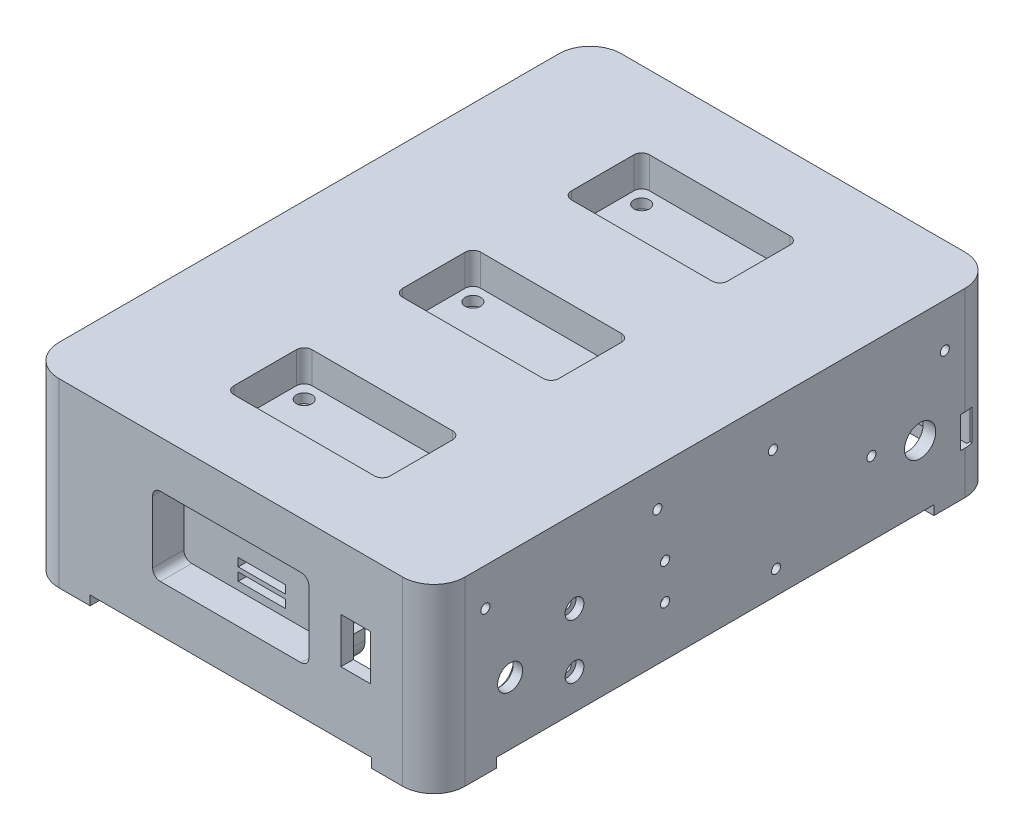
SolidWorks part; units mm, degrees
ref_plane "Спереди" through (0, 0, 0) normal (0, 0, 1) x (1, 0, 0)
ref_plane "Сверху" through (0, 0, 0) normal (0, 1, 0) x (1, 0, 0)
ref_plane "Справа" through (0, 0, 0) normal (1, 0, 0) x (0, 0, -1)
sketch "Эскиз1" plane through (0, 0, 0) normal (0, 1, 0) x (1, 0, 0)
  line L1 (-65, -90) -> (65, -90)
  line L2 (-65, -90) -> (-65, 90)
  line L3 (-65, 90) -> (65, 90)
  line L4 (65, -90) -> (65, 90)
  line L5 (-65, -90) -> (65, 90) construction
  line L6 (-65, 90) -> (65, -90) construction
  point P0 (0, 0)
  dimension "D1" = 130
  dimension "D2" = 180
extrude "Бобышка-Вытянуть1" add sketch "Эскиз1" along normal blind 55
sketch "Эскиз2" plane through (0, 0, 90) normal (0, 0, 1) x (1, 0, 0)
  line L0 (-1050, 27.5) -> (48950, 27.5) construction
  line L1 (-65, 55) -> (-65, 0) construction
  line L2 (0, -999.2777) -> (0, 49000.7223) construction
  line L4 (-22.5, 15) -> (22.5, 15)
  line L5 (-25, 17.5) -> (-25, 37.5)
  line L6 (-22.5, 40) -> (22.5, 40)
  line L7 (25, 17.5) -> (25, 37.5)
  line L8 (-25, 15) -> (25, 40) construction
  line L9 (-25, 40) -> (25, 15) construction
  arc A0 (-22.5, 40) -> (-25, 37.5) centre (-22.5, 37.5) ccw
  arc A1 (-25, 17.5) -> (-22.5, 15) centre (-22.5, 17.5) ccw
  arc A2 (25, 17.5) -> (22.5, 15) centre (22.5, 17.5) cw
  arc A3 (25, 37.5) -> (22.5, 40) centre (22.5, 37.5) ccw
  point P5 (-65, 27.5)
  point P6 (0, 27.5)
  dimension "D3" = 2.5
  dimension "D4" = 2.5
  dimension "D1" = 25
  dimension "D2" = 50
extrude "Вырез-Вытянуть1" cut sketch "Эскиз2" against normal blind 10
sketch "Эскиз4" plane through (0, 55, 0) normal (0, 1, 0) x (1, 0, 0)
  line L0 (0, -1000) -> (0, 49000) construction
  line L1 (-1000, 0) -> (49000, 0) construction
  line L2 (-22.5, 41.5) -> (22.5, 41.5)
  line L3 (-25, 44) -> (-25, 64)
  line L4 (-22.5, 66.5) -> (22.5, 66.5)
  line L5 (-22.5, -12.5) -> (22.5, -12.5)
  line L6 (-25, -10) -> (-25, 10)
  line L7 (-22.5, 12.5) -> (22.5, 12.5)
  line L8 (25, -10) -> (25, 10)
  line L9 (-25, -12.5) -> (25, 12.5) construction
  line L10 (-25, 12.5) -> (25, -12.5) construction
  line L11 (25, 44) -> (25, 64)
  line L12 (-25, 41.5) -> (25, 66.5) construction
  line L13 (-25, 66.5) -> (25, 41.5) construction
  line L14 (-25, -12.5) -> (25, -12.5) [skipped]
  line L15 (-25, -12.5) -> (-25, 12.5) [skipped]
  line L16 (-25, 12.5) -> (25, 12.5) [skipped]
  line L17 (25, -12.5) -> (25, 12.5) [skipped]
  line L18 (-25, -12.5) -> (25, 12.5) construction
  line L19 (-25, 12.5) -> (25, -12.5) construction
  line L20 (-22.5, -66.5) -> (22.5, -66.5)
  line L21 (-25, -64) -> (-25, -44)
  line L22 (-22.5, -41.5) -> (22.5, -41.5)
  line L23 (25, -64) -> (25, -44)
  line L24 (-25, -66.5) -> (25, -41.5) construction
  line L25 (-25, -41.5) -> (25, -66.5) construction
  arc A0 (22.5, -41.5) -> (25, -44) centre (22.5, -44) cw
  arc A1 (25, -64) -> (22.5, -66.5) centre (22.5, -64) cw
  arc A2 (-22.5, -66.5) -> (-25, -64) centre (-22.5, -64) cw
  arc A3 (-25, -44) -> (-22.5, -41.5) centre (-22.5, -44) cw
  arc A4 (-25, 64) -> (-22.5, 66.5) centre (-22.5, 64) cw
  arc A5 (-22.5, 12.5) -> (-25, 10) centre (-22.5, 10) ccw
  arc A6 (25, -10) -> (22.5, -12.5) centre (22.5, -10) cw
  arc A7 (22.5, 66.5) -> (25, 64) centre (22.5, 64) cw
  arc A8 (25, 44) -> (22.5, 41.5) centre (22.5, 44) cw
  arc A9 (-22.5, 41.5) -> (-25, 44) centre (-22.5, 44) cw
  arc A10 (22.5, 12.5) -> (25, 10) centre (22.5, 10) cw
  arc A11 (-22.5, -12.5) -> (-25, -10) centre (-22.5, -10) cw
  point P8 (0, 0)
  point P9 (0, 54)
  point P18 (0, 0)
  point P23 (0, -54)
  dimension "D7" = 2.5
  dimension "D8" = 2.5
  dimension "D1" = 25
  dimension "D2" = 50
  dimension "D5" = 41.5
  dimension "D6" = 41.5
  dimension "D3" = 2
  dimension "D4" = 2
extrude "Вырез-Вытянуть2" cut sketch "Эскиз4" against normal blind 10
mirror "Зеркальное отражение1" about plane through (0, 0, 0) normal (0, 0, 1) of "Вырез-Вытянуть1"
shell "Оболочка1" thickness 4 removed face at (0, 0, 0)
sketch "Эскиз5" plane through (-65, 0, 0) normal (-1, 0, 0) x (0, 0, 1)
  line L0 (45, 28.75) -> (45, 11.25) construction
  line L2 (90, 55) -> (90, 0) construction
  line L4 (-90, 0) -> (90, 0) construction
  line L7 (-1075, 20) -> (48925, 20) construction
  line L8 (-90, 55) -> (-90, 0) construction
  circle A3 centre (45, 28.75) radius 1.45
  circle A4 centre (45, 11.25) radius 1.45
  circle A5 centre (65.6, 20) radius 4
  circle A6 centre (-65.6, 20) radius 5
  dimension "D2" = 17.5
  dimension "D3" = 20
  dimension "D6" = 10
  dimension "D1" = 17.5
  dimension "D5" = 2.9
  dimension "D9" = 45
  dimension "D10" = 20.6
  dimension "D11" = 8
  dimension "D4" = 24.4
extrude "Вырез-Вытянуть3" cut sketch "Эскиз5" against normal blind 15
sketch "Эскиз6" plane through (-65, 0, 0) normal (-1, 0, 0) x (0, 0, 1)
  circle A2 centre (45, 28.75) radius 3
  circle A3 centre (45, 11.25) radius 3
  dimension "D1" = 6
extrude "Вырез-Вытянуть4" cut sketch "Эскиз6" against normal blind 2.5
sketch "Эскиз11" plane through (-61, 0, 0) normal (1, 0, 0) x (0, 0, -1)
  circle A1 centre (-65.6, 20) radius 5
  dimension "D1" = 10
extrude "Вырез-Вытянуть16" cut sketch "Эскиз11" against normal blind 1
mirror "Зеркальное отражение2" about plane through (0, 0, 0) normal (1, 0, 0) of "Вырез-Вытянуть3", "Вырез-Вытянуть4", "Вырез-Вытянуть16"
sketch "Эскиз12" plane through (0, 11, 0) normal (0, -1, 0) x (-1, 0, 0)
  line L0 (-1014.7864, -78) -> (48985.2136, -78) construction
  line L1 (22.5, -76) -> (-22.5, -76) construction
  line L2 (0, -1061) -> (0, 48939) construction
  line L3 (-10, -1061) -> (-10, 48939) construction
  line L4 (10, -1061) -> (10, 48939) construction
  circle A0 centre (-10, -78) radius 1.45
  circle A1 centre (10, -78) radius 1.45
  point P7 (0, -76)
  dimension "D4" = 2.9
  dimension "D1" = 2
  dimension "D2" = 20
  dimension "D3" = 10
extrude "Вырез-Вытянуть17" cut sketch "Эскиз12" against normal blind 14
sketch "Эскиз15" plane through (0, 45, 0) normal (0, 1, 0) x (1, 0, 0)
  line L0 (-1010.1672, -62.5) -> (48989.8328, -62.5) construction
  line L1 (0, -1031.5) -> (0, 48968.5) construction
  line L2 (-7.6, -63.8) -> (7.6, -63.8)
  line L3 (-7.6, -63.8) -> (-7.6, -61.2)
  line L4 (-7.6, -61.2) -> (7.6, -61.2)
  line L5 (7.6, -63.8) -> (7.6, -61.2)
  line L6 (-7.6, -63.8) -> (7.6, -61.2) construction
  line L7 (-7.6, -61.2) -> (7.6, -63.8) construction
  line L8 (22.5, -41.5) -> (-22.5, -41.5) construction
  line L9 (-22.5, -66.5) -> (22.5, -66.5) construction
  line L10 (-7.6, -9.8) -> (7.6, -9.8)
  line L11 (-7.6, -9.8) -> (-7.6, -7.2)
  line L12 (-7.6, -7.2) -> (7.6, -7.2)
  line L13 (7.6, -9.8) -> (7.6, -7.2)
  line L14 (-7.6, -9.8) -> (7.6, -7.2) construction
  line L15 (-7.6, -7.2) -> (7.6, -9.8) construction
  line L16 (-7.6, 44.2) -> (7.6, 44.2)
  line L17 (-7.6, 44.2) -> (-7.6, 46.8)
  line L18 (-7.6, 46.8) -> (7.6, 46.8)
  line L19 (7.6, 44.2) -> (7.6, 46.8)
  line L20 (-7.6, 44.2) -> (7.6, 46.8) construction
  line L21 (-7.6, 46.8) -> (7.6, 44.2) construction
  line L23 (22.5, 12.5) -> (-22.5, 12.5) construction
  line L24 (-7.6, -59.8) -> (7.6, -59.8)
  line L25 (-7.6, -59.8) -> (-7.6, -57.2)
  line L26 (-7.6, -57.2) -> (7.6, -57.2)
  line L27 (7.6, -59.8) -> (7.6, -57.2)
  line L28 (-7.6, -59.8) -> (7.6, -57.2) construction
  line L29 (-7.6, -57.2) -> (7.6, -59.8) construction
  line L30 (-7.6, -5.8) -> (7.6, -5.8)
  line L31 (-7.6, -5.8) -> (-7.6, -3.2)
  line L32 (-7.6, -3.2) -> (7.6, -3.2)
  line L33 (7.6, -5.8) -> (7.6, -3.2)
  line L34 (-7.6, -5.8) -> (7.6, -3.2) construction
  line L35 (-7.6, -3.2) -> (7.6, -5.8) construction
  line L36 (-7.6, 48.2) -> (7.6, 48.2)
  line L37 (-7.6, 48.2) -> (-7.6, 50.8)
  line L38 (-7.6, 50.8) -> (7.6, 50.8)
  line L39 (7.6, 48.2) -> (7.6, 50.8)
  line L40 (-7.6, 48.2) -> (7.6, 50.8) construction
  line L41 (-7.6, 50.8) -> (7.6, 48.2) construction
  line L42 (-22.5, -12.5) -> (22.5, -12.5) construction
  circle A0 centre (-20, -46.5) radius 2.5
  circle A1 centre (20, -46.5) radius 2.5
  circle A2 centre (-20, 7.5) radius 2.5
  circle A3 centre (20, 7.5) radius 2.5
  circle A4 centre (-20, 61.5) radius 2.5
  circle A5 centre (20, 61.5) radius 2.5
  point P1 (0, -62.5)
  point P12 (0, -41.5)
  point P16 (0, -8.5)
  point P21 (0, 45.5)
  point P41 (0, -4.5)
  point P42 (0, -58.5)
  point P51 (0, 49.5)
  dimension "D6" = 40
  dimension "D8" = 5
  dimension "D1" = 2.6
  dimension "D2" = 15.2
  dimension "D3" = 4
  dimension "D4" = 3
  dimension "D5" = 4
  dimension "D7" = 40
  dimension "D9" = 5
  dimension "D10" = 3
  dimension "D11" = 5
  dimension "D13" = 4
  dimension "D15" = 4
  dimension "D12" = 2
  dimension "D14" = 3
extrude "Вырез-Вытянуть20" cut sketch "Эскиз15" against normal blind 3
sketch "Эскиз16" plane through (0, 42, 0) normal (0, 1, 0) x (1, 0, 0)
  line L0 (-7.6, -62.5) -> (7.6, -62.5) construction
  line L1 (-7.6, -61.2) -> (-7.6, -63.8) construction
  line L2 (7.6, -63.8) -> (7.6, -61.2) construction
  line L3 (0, -1000) -> (0, 49000) construction
  line L4 (-7, -63.4) -> (7, -63.4)
  line L5 (-7, -63.4) -> (-7, -61.6)
  line L6 (-7, -61.6) -> (7, -61.6)
  line L7 (7, -63.4) -> (7, -61.6)
  line L8 (-7, -63.4) -> (7, -61.6) construction
  line L9 (-7, -61.6) -> (7, -63.4) construction
  line L10 (-7, -9.4) -> (7, -9.4)
  line L11 (-7, -9.4) -> (-7, -7.6)
  line L12 (-7, -7.6) -> (7, -7.6)
  line L13 (7, -9.4) -> (7, -7.6)
  line L14 (-7.6, -8.5) -> (7.6, -8.5) construction
  line L15 (-7, -9.4) -> (7, -7.6) construction
  line L16 (-7, -7.6) -> (7, -9.4) construction
  line L17 (-7, 44.6) -> (7, 44.6)
  line L18 (-7, 44.6) -> (-7, 46.4)
  line L19 (-7, 46.4) -> (7, 46.4)
  line L20 (7, 44.6) -> (7, 46.4)
  line L21 (-7.6, 45.5) -> (7.6, 45.5) construction
  line L22 (-7, 44.6) -> (7, 46.4) construction
  line L23 (-7, 46.4) -> (7, 44.6) construction
  line L24 (-7.6, -7.2) -> (-7.6, -9.8) construction
  line L25 (-7.6, -58.5) -> (7.6, -58.5) construction
  line L26 (-7, -59.4) -> (7, -59.4)
  line L27 (-7, -59.4) -> (-7, -57.6)
  line L28 (-7, -57.6) -> (7, -57.6)
  line L29 (7, -59.4) -> (7, -57.6)
  line L30 (-7, -59.4) -> (7, -57.6) construction
  line L31 (-7, -57.6) -> (7, -59.4) construction
  line L32 (-7.6, -57.2) -> (-7.6, -59.8) construction
  line L33 (7.6, -59.8) -> (7.6, -57.2) construction
  line L34 (-7.6, -4.5) -> (7.6, -4.5) construction
  line L35 (-7.6, -3.2) -> (-7.6, -5.8) construction
  line L36 (7.6, -5.8) -> (7.6, -3.2) construction
  line L37 (-7.6, -9.8) -> (7.6, -9.8) construction
  line L38 (-7, -5.4) -> (7, -5.4)
  line L39 (-7, -5.4) -> (-7, -3.6)
  line L40 (-7, -3.6) -> (7, -3.6)
  line L41 (7, -5.4) -> (7, -3.6)
  line L42 (-7, -5.4) -> (7, -3.6) construction
  line L43 (-7, -3.6) -> (7, -5.4) construction
  line L44 (7.6, -9.8) -> (7.6, -7.2) construction
  line L45 (-7.6, 46.8) -> (-7.6, 44.2) construction
  line L46 (7.6, 44.2) -> (7.6, 46.8) construction
  line L47 (-7.6, 44.2) -> (7.6, 44.2) construction
  line L48 (-7.6, 49.5) -> (7.6, 49.5) construction
  line L49 (-7.6, 50.8) -> (-7.6, 48.2) construction
  line L50 (7.6, 48.2) -> (7.6, 50.8) construction
  line L52 (-7, 48.6) -> (7, 48.6)
  line L53 (-7, 48.6) -> (-7, 50.4)
  line L54 (-7, 50.4) -> (7, 50.4)
  line L55 (7, 48.6) -> (7, 50.4)
  line L56 (-7, 48.6) -> (7, 50.4) construction
  line L57 (-7, 50.4) -> (7, 48.6) construction
  point P6 (0, -62.5)
  point P12 (0, -58.5)
  point P17 (0, -8.5)
  point P24 (0, 36.6)
  point P41 (0, -4.5)
  point P54 (0, 49.5)
  dimension "D1" = 1.8
  dimension "D2" = 14
  dimension "D4" = 0.4
  dimension "D3" = 0.4
extrude "Вырез-Вытянуть21" cut sketch "Эскиз16" against normal blind 3
sketch "Эскиз17" plane through (0, 0, 80) normal (0, 0, 1) x (1, 0, 0)
  line L0 (-7.6, 17.5) -> (7.6, 17.5)
  line L1 (-7.6, 17.5) -> (-7.6, 20.1)
  line L2 (-7.6, 20.1) -> (7.6, 20.1)
  line L3 (7.6, 17.5) -> (7.6, 20.1)
  line L4 (-7.6, 17.5) -> (7.6, 20.1) construction
  line L5 (-7.6, 20.1) -> (7.6, 17.5) construction
  line L7 (-7.6, 21.5) -> (7.6, 21.5)
  line L8 (-22.5, 15) -> (22.5, 15) construction
  line L9 (0, -965) -> (0, 49035) construction
  line L10 (22.5, 40) -> (-22.5, 40) construction
  line L11 (-7.6, 21.5) -> (-7.6, 24.1)
  line L12 (-7.6, 24.1) -> (7.6, 24.1)
  line L13 (7.6, 21.5) -> (7.6, 24.1)
  line L14 (-7.6, 21.5) -> (7.6, 24.1) construction
  line L15 (-7.6, 24.1) -> (7.6, 21.5) construction
  circle A0 centre (-20, 35) radius 2.5
  circle A1 centre (20, 35) radius 2.5
  point P0 (0, 18.8)
  point P11 (0, 22.8)
  point P20 (0, 40)
  dimension "D5" = 5
  dimension "D8" = 4
  dimension "D1" = 2.6
  dimension "D2" = 15.2
  dimension "D3" = 40
  dimension "D4" = 40
  dimension "D6" = 2.5
  dimension "D7" = 5
extrude "Вырез-Вытянуть22" cut sketch "Эскиз17" against normal blind 3
sketch "Эскиз18" plane through (0, 0, 77) normal (0, 0, 1) x (1, 0, 0)
  line L0 (-7.6, 18.8) -> (7.6, 18.8) construction
  line L1 (-7.6, 20.1) -> (-7.6, 17.5) construction
  line L2 (7.6, 17.5) -> (7.6, 20.1) construction
  line L3 (0, -980.9) -> (0, 49019.1) construction
  line L4 (-7, 17.9) -> (7, 17.9)
  line L5 (-7, 17.9) -> (-7, 19.7)
  line L6 (-7, 19.7) -> (7, 19.7)
  line L7 (7, 17.9) -> (7, 19.7)
  line L8 (-7, 17.9) -> (7, 19.7) construction
  line L9 (-7, 19.7) -> (7, 17.9) construction
  line L10 (7.6, 24.1) -> (-7.6, 24.1) construction
  line L12 (-7, 21.9) -> (7, 21.9)
  line L13 (-7, 21.9) -> (-7, 23.7)
  line L14 (-7, 23.7) -> (7, 23.7)
  line L15 (7, 21.9) -> (7, 23.7)
  line L16 (-7, 21.9) -> (7, 23.7) construction
  line L17 (-7, 23.7) -> (7, 21.9) construction
  point P6 (0, 18.8)
  point P12 (0, 22.8)
  point P16 (0, 24.1)
  dimension "D1" = 1.8
  dimension "D2" = 14
  dimension "D3" = 4
extrude "Вырез-Вытянуть23" cut sketch "Эскиз18" against normal blind 3
sketch "Эскиз19" plane through (0, 0, -80) normal (0, 0, -1) x (1, 0, 0)
  line L0 (-7.6, -37.5) -> (7.6, -37.5)
  line L1 (-7.6, -37.5) -> (-7.6, -34.9)
  line L2 (-7.6, -34.9) -> (7.6, -34.9)
  line L3 (7.6, -37.5) -> (7.6, -34.9)
  line L4 (-7.6, -37.5) -> (7.6, -34.9) construction
  line L5 (-7.6, -34.9) -> (7.6, -37.5) construction
  line L6 (0, -1010) -> (0, 48990) construction
  line L7 (-22.5, -15) -> (22.5, -15) construction
  line L9 (-7.6, -33.5) -> (7.6, -33.5)
  line L10 (22.5, -40) -> (-22.5, -40) construction
  line L11 (-7.6, -33.5) -> (-7.6, -30.9)
  line L12 (-7.6, -30.9) -> (7.6, -30.9)
  line L13 (7.6, -33.5) -> (7.6, -30.9)
  line L14 (-7.6, -33.5) -> (7.6, -30.9) construction
  line L15 (-7.6, -30.9) -> (7.6, -33.5) construction
  circle A0 centre (-20, -20) radius 2.5
  circle A1 centre (20, -20) radius 2.5
  point P0 (0, -36.2)
  point P14 (0, -15)
  point P16 (0, -32.2)
  dimension "D5" = 5
  dimension "D7" = 2.5
  dimension "D1" = 2.6
  dimension "D2" = 15.2
  dimension "D3" = 40
  dimension "D4" = 40
  dimension "D6" = 5
  dimension "D8" = 4
extrude "Вырез-Вытянуть24" cut sketch "Эскиз19" against normal blind 3
sketch "Эскиз20" plane through (0, 0, -77) normal (0, 0, -1) x (1, 0, 0)
  line L0 (-1007.6, -36.2) -> (48992.4, -36.2) construction
  line L1 (-7.6, -34.9) -> (-7.6, -37.5) construction
  line L3 (-7, -37.1) -> (7, -37.1)
  line L4 (-7, -37.1) -> (-7, -35.3)
  line L5 (-7, -35.3) -> (7, -35.3)
  line L6 (7, -37.1) -> (7, -35.3)
  line L7 (-7, -37.1) -> (7, -35.3) construction
  line L8 (-7, -35.3) -> (7, -37.1) construction
  line L9 (-7, -31.3) -> (7, -31.3)
  line L10 (0, -1029.9) -> (0, 48970.1) construction
  line L11 (7.6, -34.9) -> (-7.6, -34.9) construction
  line L12 (-7, -31.3) -> (-7, -33.1)
  line L13 (-7, -33.1) -> (7, -33.1)
  line L14 (7, -31.3) -> (7, -33.1)
  line L15 (-7, -31.3) -> (7, -33.1) construction
  line L16 (-7, -33.1) -> (7, -31.3) construction
  point P1 (0, -36.2)
  point P5 (-7.6, -36.2)
  point P10 (0, -32.2)
  point P18 (0, -34.9)
  dimension "D1" = 1.8
  dimension "D2" = 14
  dimension "D3" = 4
extrude "Вырез-Вытянуть25" cut sketch "Эскиз20" against normal blind 5
sketch "Эскиз21" plane through (0, 0, 90) normal (0, 0, -1) x (1, 0, 0)
  line L0 (-975, -27.5) -> (49025, -27.5) construction
  line L1 (35.25, -34.75) -> (44.75, -34.75)
  line L2 (35.25, -34.75) -> (35.25, -20.25)
  line L3 (35.25, -20.25) -> (44.75, -20.25)
  line L4 (44.75, -34.75) -> (44.75, -20.25)
  line L5 (35.25, -34.75) -> (44.75, -20.25) construction
  line L6 (35.25, -20.25) -> (44.75, -34.75) construction
  line L7 (25, -17.5) -> (25, -37.5) construction
  line L8 (40, -1022.5) -> (40, 48977.5) construction
  line L9 (65, -55) -> (65, 0) construction
  point P0 (40, -27.5)
  point P10 (25, -27.5)
  dimension "D1" = 9.5
  dimension "D2" = 14.5
  dimension "D3" = 25
extrude "Вырез-Вытянуть26" cut sketch "Эскиз21" along normal blind 4
sketch "Эскиз22" plane through (0, 0, 0) normal (0, -1, 0) x (-1, 0, 0)
  line L0 (-63, -925) -> (-63, 49075) construction
  line L2 (-65, -90) -> (-65, 90) construction
  line L3 (-1046.2998, 88) -> (48953.7002, 88) construction
  line L4 (-65, 90) -> (65, 90) construction
  line L5 (63, -925) -> (63, 49075) construction
  line L6 (65, 90) -> (65, -90) construction
  line L7 (-1052.5, -88) -> (48947.5, -88) construction
  line L8 (65, -90) -> (-65, -90) construction
  line L9 (0, -925) -> (0, 49075) construction
  line L10 (-1052.5, 0) -> (48947.5, 0) construction
  circle A4 centre (0, 88) radius 1.425
  circle A5 centre (0, -88) radius 1.425
  circle A6 centre (-63, 0) radius 1.425
  circle A7 centre (63, 0) radius 1.425
  point P27 (0, 90)
  point P34 (-65, 0)
  dimension "D5" = 2.85
  dimension "D1" = 2
  dimension "D2" = 2
  dimension "D3" = 2
  dimension "D4" = 2
extrude "Вырез-Вытянуть27" cut sketch "Эскиз22" against normal blind 9
sketch "Эскиз24" plane through (-65, 0, 0) normal (-1, 0, 0) x (0, 0, 1)
  line L0 (0, -1000) -> (0, 49000) construction
  line L1 (16, -988.2808) -> (16, 49011.7192) construction
  line L2 (-90, 0) -> (90, 0) construction
  circle A0 centre (16, 16) radius 1.475
  circle A1 centre (16, 27.5) radius 1.475
  dimension "D4" = 2.95
  dimension "D1" = 11.5
  dimension "D2" = 16
  dimension "D3" = 16
extrude "Вырез-Вытянуть28" cut sketch "Эскиз24" against normal through all
fillet "Скругление1" radius 10 4 edges at (65, 27.5, -90) (-65, 27.5, -90) (65, 27.5, 90) (-65, 27.5, 90)
sketch "Эскиз26" plane through (61, 0, 0) normal (-1, 0, 0) x (0, 0, 1)
  line L1 (17.6454, 18.85) -> (14.3546, 18.85)
  line L2 (14.3546, 18.85) -> (12.7091, 16)
  line L3 (12.7091, 16) -> (14.3546, 13.15)
  line L4 (14.3546, 13.15) -> (17.6454, 13.15)
  line L5 (17.6454, 13.15) -> (19.2909, 16)
  line L6 (19.2909, 16) -> (17.6454, 18.85)
  line L7 (17.6454, 30.35) -> (14.3546, 30.35)
  line L8 (14.3546, 30.35) -> (12.7091, 27.5)
  line L9 (12.7091, 27.5) -> (14.3546, 24.65)
  line L10 (14.3546, 24.65) -> (17.6454, 24.65)
  line L11 (17.6454, 24.65) -> (19.2909, 27.5)
  line L12 (19.2909, 27.5) -> (17.6454, 30.35)
  circle A0 centre (16, 16) radius 2.85 construction
  circle A1 centre (16, 27.5) radius 2.85 construction
  dimension "D1" = 5.7
extrude "Вырез-Вытянуть29" cut sketch "Эскиз26" against normal blind 2 and the other way blind 124
fillet "Скругление2" radius 3 4 edges at (61, 25.5, 86) (61, 25.5, -86) (-61, 25.5, -86) (-61, 25.5, 86)
sketch "Эскиз27" plane through (0, 0, 0) normal (0, -1, 0) x (1, 0, 0)
  line L0 (-55, -90) -> (-45, -90)
  line L1 (55, -90) -> (-55, -90) construction
  line L2 (-45, -90) -> (-45, -86)
  line L3 (58, -86) -> (-58, -86) construction
  line L4 (-45, -86) -> (-58, -86)
  line L6 (-61, -83) -> (-61, -70)
  line L7 (-61, -83) -> (-61, 83) construction
  line L8 (-61, -70) -> (-65, -70)
  line L9 (-65, -80) -> (-65, 80) construction
  line L10 (-65, -70) -> (-65, -80)
  line L11 (0, -1000) -> (0, 49000) construction
  line L12 (-1000, 0) -> (49000, 0) construction
  line L13 (65, -70) -> (65, -80)
  line L14 (61, -70) -> (65, -70)
  line L15 (61, -83) -> (61, -70)
  line L16 (45, -86) -> (58, -86)
  line L17 (45, -90) -> (45, -86)
  line L18 (55, -90) -> (45, -90)
  line L19 (55, 90) -> (45, 90)
  line L20 (45, 90) -> (45, 86)
  line L21 (45, 86) -> (58, 86)
  line L22 (61, 83) -> (61, 70)
  line L23 (61, 70) -> (65, 70)
  line L24 (65, 70) -> (65, 80)
  line L25 (-65, 70) -> (-65, 80)
  line L26 (-61, 70) -> (-65, 70)
  line L27 (-61, 83) -> (-61, 70)
  line L28 (-45, 86) -> (-58, 86)
  line L29 (-45, 90) -> (-45, 86)
  line L30 (-55, 90) -> (-45, 90)
  arc A1 (-65, -80) -> (-55, -90) centre (-55, -80) ccw construction
  arc A4 (61, -83) -> (58, -86) centre (58, -83) cw
  arc A5 (-65, -80) -> (-55, -90) centre (-55, -80) ccw
  arc A6 (65, -80) -> (55, -90) centre (55, -80) cw
  arc A7 (-61, 83) -> (-58, 86) centre (-58, 83) cw
  arc A8 (-61, -83) -> (-58, -86) centre (-58, -83) ccw construction
  arc A9 (-61, -83) -> (-58, -86) centre (-58, -83) ccw
  arc A10 (65, 80) -> (55, 90) centre (55, 80) ccw
  arc A11 (-65, 80) -> (-55, 90) centre (-55, 80) cw
  arc A12 (61, 83) -> (58, 86) centre (58, 83) ccw
  dimension "D1" = 10
extrude "Бобышка-Вытянуть2" add sketch "Эскиз27" along normal blind 3
sketch "Эскиз28" plane through (0, 0, 0) normal (0, -1, 0) x (1, 0, 0)
  line L0 (-61, 70) -> (-61, 83) construction
  line L2 (-61, 70) -> (-61, 83)
  line L3 (-58, 86) -> (-45, 86)
  line L4 (-45, 86) -> (-45, 86.5)
  line L5 (-45, 86) -> (-45, 90) construction
  line L6 (-45, 86.5) -> (-58, 86.5)
  line L7 (-1000, 0) -> (49000, 0) construction
  line L8 (-61.5, 83) -> (-61.5, 70)
  line L9 (-65, 70) -> (-61, 70) construction
  line L10 (-61.5, 70) -> (-61, 70)
  line L11 (0, -1000) -> (0, 49000) construction
  line L12 (61.5, 70) -> (61, 70)
  line L13 (61.5, 83) -> (61.5, 70)
  line L14 (45, 86.5) -> (58, 86.5)
  line L15 (45, 86) -> (45, 86.5)
  line L16 (58, 86) -> (45, 86)
  line L17 (61, 70) -> (61, 83)
  line L18 (61, -70) -> (61, -83)
  line L19 (58, -86) -> (45, -86)
  line L20 (45, -86) -> (45, -86.5)
  line L21 (45, -86.5) -> (58, -86.5)
  line L22 (61.5, -83) -> (61.5, -70)
  line L23 (61.5, -70) -> (61, -70)
  line L24 (-61.5, -70) -> (-61, -70)
  line L25 (-61.5, -83) -> (-61.5, -70)
  line L26 (-45, -86.5) -> (-58, -86.5)
  line L27 (-45, -86) -> (-45, -86.5)
  line L28 (-58, -86) -> (-45, -86)
  line L29 (-61, -70) -> (-61, -83)
  arc A0 (-58, 86) -> (-61, 83) centre (-58, 83) ccw construction
  arc A1 (-58, 86) -> (-61, 83) centre (-58, 83) ccw
  arc A2 (-61.5, 83) -> (-58, 86.5) centre (-58, 83) cw
  arc A3 (61.5, 83) -> (58, 86.5) centre (58, 83) ccw
  arc A4 (58, 86) -> (61, 83) centre (58, 83) cw
  arc A5 (58, -86) -> (61, -83) centre (58, -83) ccw
  arc A6 (61.5, -83) -> (58, -86.5) centre (58, -83) cw
  arc A7 (-61.5, -83) -> (-58, -86.5) centre (-58, -83) ccw
  arc A8 (-58, -86) -> (-61, -83) centre (-58, -83) cw
  dimension "D1" = 0.5
extrude "Вырез-Вытянуть30" cut sketch "Эскиз28" along normal blind 2.5
sketch "Эскиз30" plane through (0, 51, 0) normal (0, -1, 0) x (1, 0, 0)
  line L0 (-29, -10) -> (-29, 10) construction
  line L1 (-58.5, 86) -> (-29, 86)
  line L2 (-61, 83.5) -> (-61, 6)
  line L3 (-61, 6) -> (-29, 6)
  line L4 (-29, 86) -> (-29, 6)
  line L5 (-58, 86) -> (58, 86) construction
  line L6 (-61, -83) -> (-61, 83) construction
  line L7 (0, -1000) -> (0, 49000) construction
  line L8 (29, 86) -> (29, 6)
  line L9 (61, 6) -> (29, 6)
  line L10 (61, 83.5) -> (61, 6)
  line L11 (58.5, 86) -> (29, 86)
  arc A0 (-58.5, 86) -> (-61, 83.5) centre (-58.5, 83.5) ccw
  arc A1 (58.5, 86) -> (61, 83.5) centre (58.5, 83.5) cw
  dimension "D1" = 2.5
  dimension "D2" = 80
extrude "Вырез-Вытянуть32" cut sketch "Эскиз30" against normal blind 2
sketch "Эскиз29" plane through (-61, 0, 0) normal (1, 0, 0) x (0, 0, -1)
  line L1 (83, 51) -> (-6, 51) construction
  line L2 (-86, 0) -> (-86, 51) construction
  line L3 (0, -1000) -> (0, 49000) construction
  line L4 (90, 55) -> (90, -3) construction
  line L6 (-80, 55) -> (80, 55) construction
  circle A0 centre (-73.5, 43) radius 1.45
  circle A1 centre (-18.5, 43) radius 1.45
  circle A4 centre (18.5, 41) radius 1.45
  circle A5 centre (73.5, 41) radius 1.45
  dimension "D1" = 8
  dimension "D4" = 2.9
  dimension "D5" = 55
  dimension "D2" = 12.5
  dimension "D3" = 55
  dimension "D6" = 16.5
  dimension "D7" = 14
extrude "Вырез-Вытянуть31" cut sketch "Эскиз29" against normal through all both and the other way through all
sketch "Эскиз31" plane through (0, 41, 0) normal (0, -1, 0) x (1, 0, 0)
  line L0 (26, -1043.9084) -> (26, 48956.0916) construction
  line L2 (29, 64) -> (29, 44) construction
  line L3 (29, -76) -> (29, -86) construction
  line L4 (26, 81) -> (29, 81)
  line L5 (26, 81) -> (26, -81)
  line L6 (26, -81) -> (29, -81)
  line L7 (29, 81) -> (29, -81)
  line L8 (22.5, 76) -> (22.5, 86) construction
  line L9 (-977.5, 81) -> (49022.5, 81) construction
  line L10 (0, -1000) -> (0, 49000) construction
  line L11 (-26, -1043.9084) -> (-26, 48956.0916) construction
  line L12 (-29, 81) -> (-29, -81)
  line L13 (-26, -81) -> (-29, -81)
  line L14 (-26, 81) -> (-26, -81)
  line L15 (-26, 81) -> (-29, 81)
  point P16 (22.5, 81)
  dimension "D1" = 3
extrude "Вырез-Вытянуть33" cut sketch "Эскиз31" against normal up to surface (10 mm away) and the other way blind 20 up to face at (0, 51, 27)
sketch "Эскиз32" plane through (61, 0, 0) normal (-1, 0, 0) x (0, 0, 1)
  line L0 (-83, 51) -> (-83, 0) construction
  line L1 (-83, 7) -> (-81.5, 7)
  line L2 (-83, 7) -> (-83, 24.5)
  line L3 (-83, 24.5) -> (-81.5, 24.5)
  line L4 (-81.5, 7) -> (-81.5, 24.5)
  line L5 (83, 0) -> (-83, 0) construction
  dimension "D1" = 17.5
  dimension "D2" = 1.5
  dimension "D3" = 7
extrude "Вырез-Вытянуть34" cut sketch "Эскиз32" against normal blind 3 contours L1 L4 L3 L2
sketch "Эскиз33" plane through (61, 0, 0) normal (-1, 0, 0) x (0, 0, 1)
  line L0 (-81.5, 7) -> (-81.5, 24.5) construction
  line L1 (-82.5, 20.75) -> (-78.5, 20.75)
  line L2 (-82.5, 20.75) -> (-82.5, 10.75)
  line L3 (-82.5, 10.75) -> (-78.5, 10.75)
  line L4 (-78.5, 20.75) -> (-78.5, 10.75)
  line L5 (-1081.5, 15.75) -> (48918.5, 15.75) construction
  point P7 (-78.5, 15.75)
  point P9 (-81.5, 15.75)
  dimension "D1" = 10
  dimension "D2" = 4
  dimension "D3" = 3
extrude "Вырез-Вытянуть35" cut sketch "Эскиз33" against normal blind 4
sketch "Эскиз34" plane through (0, 0, -86) normal (0, 0, 1) x (1, 0, 0)
  line L0 (61, 51) -> (61, 24.5) construction
  line L1 (34, 7) -> (61, 7)
  line L2 (34, 7) -> (34, 24.5)
  line L3 (34, 24.5) -> (61, 24.5)
  line L4 (61, 7) -> (61, 24.5)
  line L5 (58, 0) -> (-58, 0) construction
  dimension "D1" = 7
  dimension "D2" = 27
  dimension "D3" = 17.5
extrude "Бобышка-Вытянуть3" add sketch "Эскиз34" along normal blind 3
sketch "Эскиз35" plane through (61, 0, 0) normal (-1, 0, 0) x (0, 0, 1)
  line L0 (-90, 55) -> (-90, -3) construction
  line L1 (83, 0) -> (-83, 0) construction
  circle A0 centre (-50, 23.5) radius 1.45
  circle A1 centre (-19.5, 7.5) radius 1.45
  dimension "D1" = 16
  dimension "D5" = 2.9
  dimension "D2" = 30.5
  dimension "D3" = 40
  dimension "D4" = 7.5
extrude "Вырез-Вытянуть36" cut sketch "Эскиз35" against normal blind 4
sketch "Эскиз36" plane through (0, 41, 0) normal (0, -1, 0) x (1, 0, 0)
  line L0 (-22.5, 16.5) -> (22.5, 16.5) construction
  line L1 (-17.5, 16.5) -> (17.5, 16.5)
  line L2 (-17.5, 16.5) -> (-17.5, 21.5)
  line L3 (-17.5, 21.5) -> (17.5, 21.5)
  line L4 (17.5, 16.5) -> (17.5, 21.5)
  line L5 (0, -990.6) -> (0, 49009.4) construction
  line L6 (-7, 9.4) -> (7, 9.4) construction
  point P7 (0, 21.5)
  point P11 (0, 9.4)
  dimension "D1" = 5
  dimension "D2" = 35
extrude "Бобышка-Вытянуть4" add sketch "Эскиз36" against normal up to surface (10 mm away)
sketch "Эскиз37" plane through (0, 41, 0) normal (0, -1, 0) x (1, 0, 0)
  line L0 (-14.5, -981.9998) -> (-14.5, 49018.0002) construction
  line L1 (14.5, -981.9998) -> (14.5, 49018.0002) construction
  line L2 (17.5, 21.5) -> (-17.5, 21.5) construction
  circle A0 centre (-14.5, 19.5) radius 1.45
  circle A1 centre (14.5, 19.5) radius 1.45
  dimension "D3" = 2.9
  dimension "D1" = 29
  dimension "D2" = 14.5
  dimension "D4" = 2
extrude "Вырез-Вытянуть37" cut sketch "Эскиз37" against normal blind 6
sketch "Эскиз38" plane through (-61, 0, 0) normal (1, 0, 0) x (0, 0, -1)
  line L0 (-3.9, -995.0619) -> (-3.9, 49004.9381) construction
  line L1 (52, -995.0619) -> (52, 49004.9381) construction
  line L2 (-1004.5398, 26.8) -> (48995.4602, 26.8) construction
  line L3 (-1004.5398, 8) -> (48995.4602, 8) construction
  line L4 (83, 0) -> (-83, 0) construction
  line L5 (86, 51) -> (86, 0) construction
  circle A0 centre (-3.9, 26.8) radius 1.45
  circle A1 centre (-3.9, 8) radius 1.45
  circle A2 centre (52, 8) radius 1.45
  circle A3 centre (52, 26.8) radius 1.45
  point P21 (51.5778, -22.6418)
  point P22 (-1.764, 5.3736)
  dimension "D3" = 2.9
  dimension "D1" = 55.9
  dimension "D2" = 18.8
  dimension "D4" = 8
  dimension "D5" = 34
extrude "Вырез-Вытянуть38" cut sketch "Эскиз38" against normal blind 10
sketch "Эскиз39" plane through (0, 41, 0) normal (0, -1, 0) x (1, 0, 0)
  line L1 (-26, -4) -> (-21, -4)
  line L2 (-26, -4) -> (-26, -11.5)
  line L3 (-26, -11.5) -> (-21, -11.5)
  line L4 (-21, -4) -> (-21, -11.5)
  line L5 (-26, -15.4772) -> (-26, 15.4772) construction
  line L6 (22.5, -16.5) -> (-22.5, -16.5) construction
  line L7 (-26, -38.5228) -> (-26, -69.4772) construction
  line L8 (-26, -61) -> (-21, -61)
  line L9 (-26, -61) -> (-26, -68.5)
  line L10 (-26, -68.5) -> (-21, -68.5)
  line L11 (-21, -61) -> (-21, -68.5)
  line L12 (22.5, -70.5) -> (-22.5, -70.5) construction
  line L13 (0, -1000) -> (0, 49000) construction
  line L14 (21, -61) -> (21, -68.5)
  line L15 (26, -68.5) -> (21, -68.5)
  line L16 (26, -61) -> (26, -68.5)
  line L17 (26, -61) -> (21, -61)
  line L18 (21, -4) -> (21, -11.5)
  line L19 (26, -11.5) -> (21, -11.5)
  line L20 (26, -4) -> (26, -11.5)
  line L21 (26, -4) -> (21, -4)
  dimension "D1" = 5
  dimension "D2" = 5
  dimension "D3" = 7.5
  dimension "D4" = 2
  dimension "D5" = 7.5
extrude "Бобышка-Вытянуть5" add sketch "Эскиз39" along normal blind 10
sketch "Эскиз40" plane through (0, 31, 0) normal (0, -1, 0) x (1, 0, 0)
  line L0 (0, -1000) -> (0, 49000) construction
  line L1 (-24.5, -1009.0693) -> (-24.5, 48990.9307) construction
  line L2 (-26, -68.5) -> (-21, -68.5) construction
  circle A0 centre (-24.5, -8.5) radius 1.45
  circle A1 centre (-24.5, -66) radius 1.45
  circle A2 centre (24.5, -66) radius 1.45
  circle A3 centre (24.5, -8.5) radius 1.45
  dimension "D2" = 57.5
  dimension "D4" = 2.9
  dimension "D1" = 24.5
  dimension "D3" = 2.5
extrude "Вырез-Вытянуть39" cut sketch "Эскиз40" against normal blind 6
